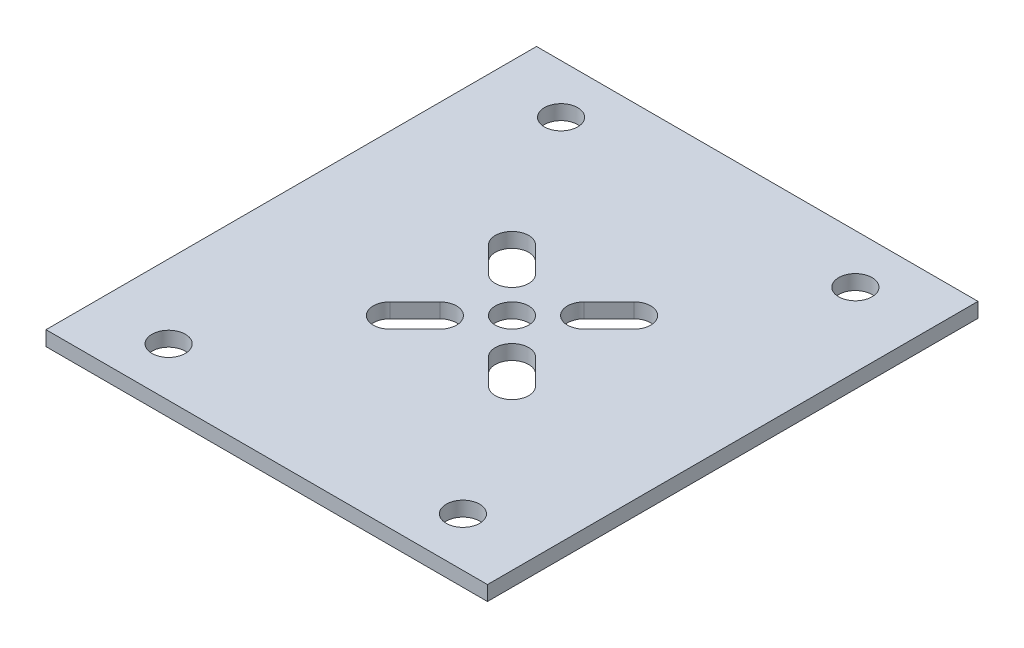
SolidWorks part; units mm, degrees
material "Thornel Mat VMA"
ref_plane "Front Plane" through (0, 0, 0) normal (0, 0, 1) x (1, 0, 0)
ref_plane "Top Plane" through (0, 0, 0) normal (0, 1, 0) x (1, 0, 0)
ref_plane "Right Plane" through (0, 0, 0) normal (1, 0, 0) x (0, 0, -1)
sketch "Sketch2" plane through (0, 0, 0) normal (0, 1, 0) x (1, 0, 0)
  line L1 (-22.5, -25) -> (22.5, -25)
  line L2 (-22.5, -25) -> (-22.5, 25)
  line L3 (-22.5, 25) -> (22.5, 25)
  line L4 (22.5, -25) -> (22.5, 25)
  point P0 (0, 0)
  dimension "D1" = 50
  dimension "D2" = 45
  dimension "D3" = 22.5
  dimension "D4" = 25
extrude "Boss-Extrude1" add sketch "Sketch2" along normal blind 1.5
hole_wizard "M3 Clearance Hole" positions "Sketch7" profile "Sketch8" hole size "M3" standard "ANSI Metric" end condition up to next
sketch "Sketch7" plane through (0, 1.5, 0) normal (0, 1, 0) x (1, 0, 0)
  point P0 (-15, 20)
  point P2 (15, 20)
  point P4 (15, -20)
  point P6 (-15, -20)
  point P16 (0, 0)
  dimension "D1" = 20
  dimension "D2" = 30
  dimension "D3" = 40
  dimension "D4" = 15
sketch "Sketch8" plane through (-15, 1.5, -20) normal (1, 0, 0) x (0, 0, 1)
  line L0 (0, 0) -> (0, 1.5)
  line L1 (0, 1.5) -> (1.7, 1.5)
  line L2 (1.7, 1.5) -> (1.7, 0)
  line L5 (1.7, 0) -> (0, 0)
  line L11 (0, -6.35) -> (0, 107.95) construction
  dimension "Thru Hole Dia." = 3.4
  dimension "Thru Hole Depth" = 1.5
hole_wizard "M3 Clearance Slot1" positions "Sketch11" profile "Sketch12" size "M3" standard "ANSI Metric" slot yes end condition up to next
sketch "Sketch11" plane through (0, 1.5, 0) normal (0, 1, 0) x (1, 0, 0)
  line L1 (-7.4246, 7.4246) -> (-2.4749, 2.4749) construction
  line L2 (-22.5, 25) -> (-22.5, -25) construction
  line L3 (-2.4749, 2.4749) -> (4.9497, -4.9497) construction
  point P0 (-4.9497, 4.9497)
  point P13 (4.9497, -4.9497)
  dimension "D1" = 7
  dimension "D2" = 45
  dimension "D3" = 7
  dimension "D4" = 7
sketch "Sketch12" plane through (-4.9497, 1.5, -4.9497) normal (1, 0, 0) x (0, 0, 1)
  line L0 (0, 0) -> (0, 1.5)
  line L1 (0, 1.5) -> (1.7, 1.5)
  line L2 (1.7, 1.5) -> (1.7, 0)
  line L5 (1.7, 0) -> (0, 0)
  line L11 (0, -6.35) -> (0, 107.95) construction
  dimension "Thru Hole Dia." = 3.4
  dimension "Thru Hole Depth" = 1.5
hole_wizard "M3 Clearance Slot2" positions "Sketch13" profile "Sketch14" size "M3" standard "ANSI Metric" slot yes end condition up to next
sketch "Sketch13" plane through (0, 1.5, 0) normal (0, 1, 0) x (1, 0, 0)
  line L0 (2.4749, 2.4749) -> (7.4246, 7.4246) construction
  line L1 (22.5, -25) -> (22.5, 25) construction
  line L2 (2.4749, 2.4749) -> (-4.9497, -4.9497) construction
  point P0 (4.9497, 4.9497)
  point P4 (-4.9497, -4.9497)
  dimension "D1" = 7
  dimension "D2" = 45
  dimension "D3" = 7
  dimension "D4" = 7
sketch "Sketch14" plane through (4.9497, 1.5, -4.9497) normal (1, 0, 0) x (0, 0, 1)
  line L0 (0, 0) -> (0, 1.5)
  line L1 (0, 1.5) -> (1.7, 1.5)
  line L2 (1.7, 1.5) -> (1.7, 0)
  line L5 (1.7, 0) -> (0, 0)
  line L11 (0, -6.35) -> (0, 107.95) construction
  dimension "Thru Hole Dia." = 3.4
  dimension "Thru Hole Depth" = 1.5
